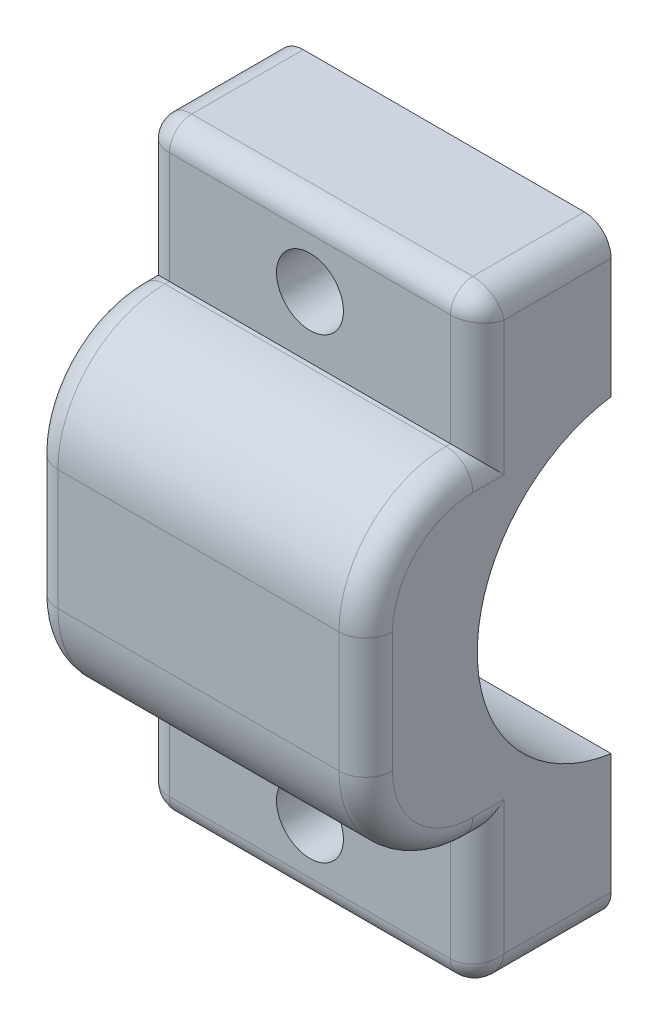
SolidWorks part; units mm, degrees
ref_plane "Plan de face" through (0, 0, 0) normal (0, 0, 1) x (1, 0, 0)
ref_plane "Plan de dessus" through (0, 0, 0) normal (0, 1, 0) x (1, 0, 0)
ref_plane "Plan de droite" through (0, 0, 0) normal (1, 0, 0) x (0, 0, -1)
sketch "Esquisse1" plane through (0, 0, 0) normal (0, 0, 1) x (1, 0, 0)
  line L1 (7.5, 13.5) -> (-7.5, 13.5)
  line L2 (7.5, 13.5) -> (7.5, -13.5)
  line L3 (7.5, -13.5) -> (-7.5, -13.5)
  line L4 (-7.5, 13.5) -> (-7.5, -13.5)
  line L5 (7.5, 13.5) -> (-7.5, -13.5) construction
  line L6 (7.5, -13.5) -> (-7.5, 13.5) construction
  point P0 (0, 0)
  dimension "D1" = 15
  dimension "D2" = 27
extrude "BASE" add sketch "Esquisse1" along normal blind 12
sketch "Esquisse2" plane through (-7.5, 0, 0) normal (-1, 0, 0) x (0, 0, 1)
  line L0 (0, 13.5) -> (0, -13.5) construction
  arc A0 (0, 7) -> (0, -7) centre (0, 0) cw
  dimension "D1" = 7
extrude "Passage_Guidon" cut sketch "Esquisse2" against normal blind 15 and the other way through all flip side to cut
sketch "Esquisse5" plane through (0, 0, 12) normal (0, 0, 1) x (1, 0, 0)
  line L0 (7.5, 13.5) -> (-7.5, 13.5) construction
  line L1 (55, 0) -> (-55, 0) construction
  circle A0 centre (0, 10.25) radius 1.5
  circle A1 centre (0, -10.25) radius 1.5
  dimension "D1" = 3
  dimension "D2" = 3.25
extrude "Passage_Vis" cut sketch "Esquisse5" against normal up to next
sketch "Esquisse7" plane through (-7.5, 0, 0) normal (-1, 0, 0) x (0, 0, 1)
  line L0 (0, 13.5) -> (0, 7) construction
  line L1 (12, 13.5) -> (7, 13.5)
  line L2 (12, 13.5) -> (12, 7.5)
  line L3 (12, 7.5) -> (7, 7.5)
  line L4 (7, 13.5) -> (7, 7.5)
  line L5 (55, 0) -> (-55, 0) construction
  line L6 (12, -7.5) -> (7, -7.5)
  line L7 (7, -13.5) -> (7, -7.5)
  line L8 (12, -13.5) -> (7, -13.5)
  line L9 (12, -13.5) -> (12, -7.5)
  dimension "D1" = 6
  dimension "D2" = 7
extrude "Reduction" cut sketch "Esquisse7" against normal up to next
fillet "Congé1" radius 1 2 edges at (0, 13.5, 7) (0, -13.5, 7)
fillet "Congé2" radius 4.8 2 edges at (0, 7.5, 12) (0, -7.5, 12)
fillet "Congé3" radius 1.2 22 edges at (-7.5, 13.5, 3) (-7.5, 13.2071, 6.7071) (-7.5, 10, 7) (-7.5, 6.0941, 10.5941) (-7.5, 0, 12) (-7.5, -6.0941, 10.5941) (-7.5, -10, 7) (-7.5, -13.2071, 6.7071) (7.5, 13.5, 3) (7.5, 13.2071, 6.7071) (7.5, 10, 7) (7.5, 6.0941, 10.5941) (7.5, 0, 12) (7.5, -6.0941, 10.5941) (7.5, -10, 7) (7.5, -13.2071, 6.7071) (-7.5, -13.5, 3) (7.5, -13.5, 3) (-7.5, -7.5, 7.1) (7.5, -7.5, 7.1) (7.5, 7.5, 7.1) (-7.5, 7.5, 7.1)
sketch "Esquisse8" plane through (0, 0, 0) normal (1, 0, 0) x (0, 0, -1)
  line L0 (0, -13.5) -> (-6, -13.5) construction
  line L1 (0, 13.5) -> (-1, 13.5)
  line L2 (0, 13.5) -> (0, -13.5)
  line L3 (0, -13.5) -> (-1, -13.5)
  line L4 (-1, 13.5) -> (-1, -13.5)
  point P7 (0, 0)
  point P8 (2.26, 14.3911)
  point P10 (0, 0)
  point P11 (0.3485, 12.6725)
  point P13 (0, 0)
  point P14 (2.2485, 11.5729)
  point P15 (0, 13.6709)
  point P16 (-0.3005, 13.8254)
  point P17 (0.2077, 13.5656)
  point P18 (0, 0)
  dimension "D1" = 1
extrude "Raccourcis_Serrage" cut sketch "Esquisse8" against normal mid plane 15
